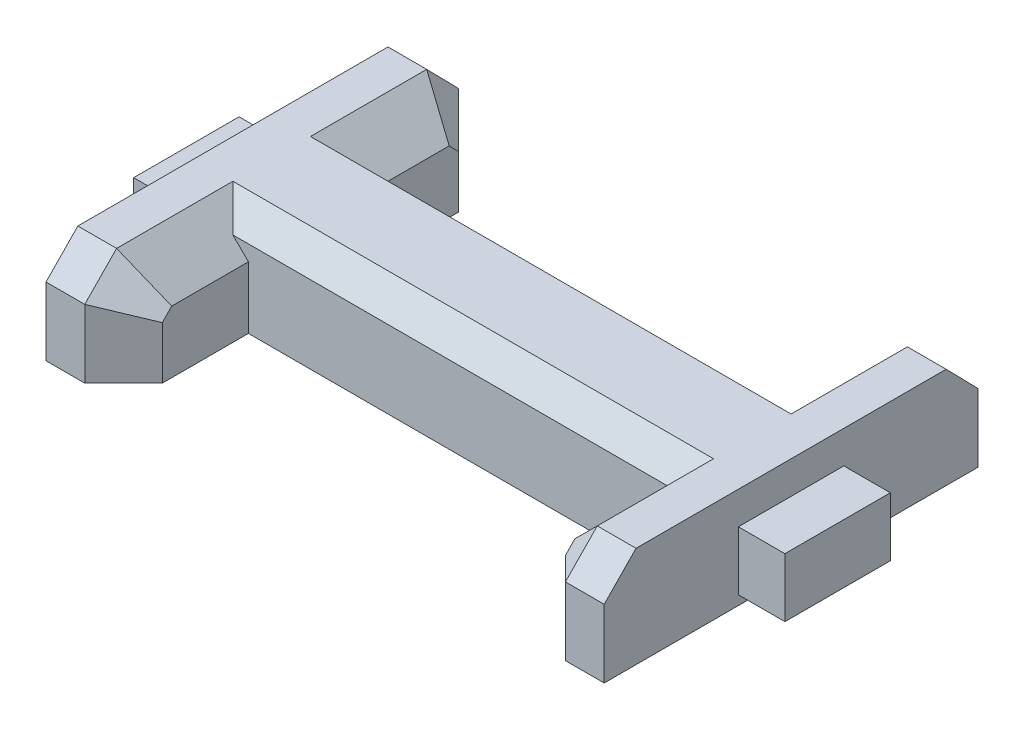
SolidWorks part; units mm, degrees
ref_plane "Front Plane" through (0, 0, 0) normal (0, 0, 1) x (1, 0, 0)
ref_plane "Top Plane" through (0, 0, 0) normal (0, 1, 0) x (1, 0, 0)
ref_plane "Right Plane" through (0, 0, 0) normal (1, 0, 0) x (0, 0, -1)
sketch "Sketch1" plane through (0, 0, 0) normal (0, 1, 0) x (1, 0, 0)
  line L1 (-18, -4) -> (18, -4)
  line L2 (-18, -4) -> (-18, 4)
  line L3 (-18, 4) -> (18, 4)
  line L4 (18, -4) -> (18, 4)
  line L5 (-18, -4) -> (18, 4) construction
  line L6 (-18, 4) -> (18, -4) construction
  point P0 (0, 0)
  dimension "D1" = 8
  dimension "D2" = 36
extrude "Boss-Extrude1" add sketch "Sketch1" along normal blind 2.5 and the other way blind 2.5
sketch "Sketch2" plane through (0, 0, 0) normal (0, 1, 0) x (1, 0, 0)
  line L1 (-21, 3.4) -> (21, 3.4)
  line L2 (-21, 3.4) -> (-21, -3.4)
  line L3 (-21, -3.4) -> (21, -3.4)
  line L4 (21, 3.4) -> (21, -3.4)
  line L5 (-21, 3.4) -> (21, -3.4) construction
  line L6 (-21, -3.4) -> (21, 3.4) construction
  point P0 (0, 0)
  dimension "D1" = 42
  dimension "D2" = 6.8
extrude "Boss-Extrude2" add sketch "Sketch2" along normal blind 1.9 and the other way blind 1.9
sketch "Sketch3" plane through (0, 0, 0) normal (1, 0, 0) x (0, 0, -1)
  line L8 (-4, 2.5) -> (-2.5, 4)
  line L9 (-2.5, 4) -> (2.5, 4)
  line L10 (0, 4) -> (0, 2.5) construction
  line L11 (-4, 2.5) -> (4, 2.5) construction
  line L12 (4, 2.5) -> (2.5, 4)
  line L13 (-4, 2.5) -> (4, 2.5)
  dimension "D1" = 1.5
  dimension "D2" = 5
extrude "Boss-Extrude4" add sketch "Sketch3" along normal blind 18 and the other way blind 18
sketch "Sketch4" plane through (18, 0, 0) normal (1, 0, 0) x (0, 0, -1)
  line L0 (10, 4) -> (-10, 4)
  line L1 (2.5, 4) -> (-2.5, 4) construction
  line L2 (-10, 4) -> (-12.054, 1.9)
  line L3 (-12.054, 1.9) -> (-12.054, -2.5)
  line L4 (-12.054, -2.5) -> (12.054, -2.5)
  line L5 (0, -2.5) -> (0, 4) construction
  line L6 (-4, -2.5) -> (4, -2.5) construction
  line L7 (3.4, 1.9) -> (-3.4, 1.9) construction
  line L8 (12.054, 1.9) -> (12.054, -2.5)
  line L9 (10, 4) -> (12.054, 1.9)
  point P5 (0, 3.7457)
  dimension "D1" = 0
  dimension "D2" = 0
extrude "Boss-Extrude5" add sketch "Sketch4" against normal blind 5
ref_plane "Plane1" through (0, 0, 0) normal (1, 0, 0) x (0, 0, -1)
mirror "Mirror1" about plane through (0, 0, 0) normal (1, 0, 0) of "Boss-Extrude5"
chamfer "Chamfer1" distance 2.5 angle 45 12 edges at (13, -0.3, -12.054) (13, 4, -6.25) (13, -0.3, 12.054) (13, 4, 6.25) (-13, -0.3, -12.054) (-13, 4, -6.25) (-13, -0.3, 12.054) (-13, 4, 6.25) (13, 2.95, -11.027) (13, 2.95, 11.027) (-13, 2.95, -11.027) (-13, 2.95, 11.027)
